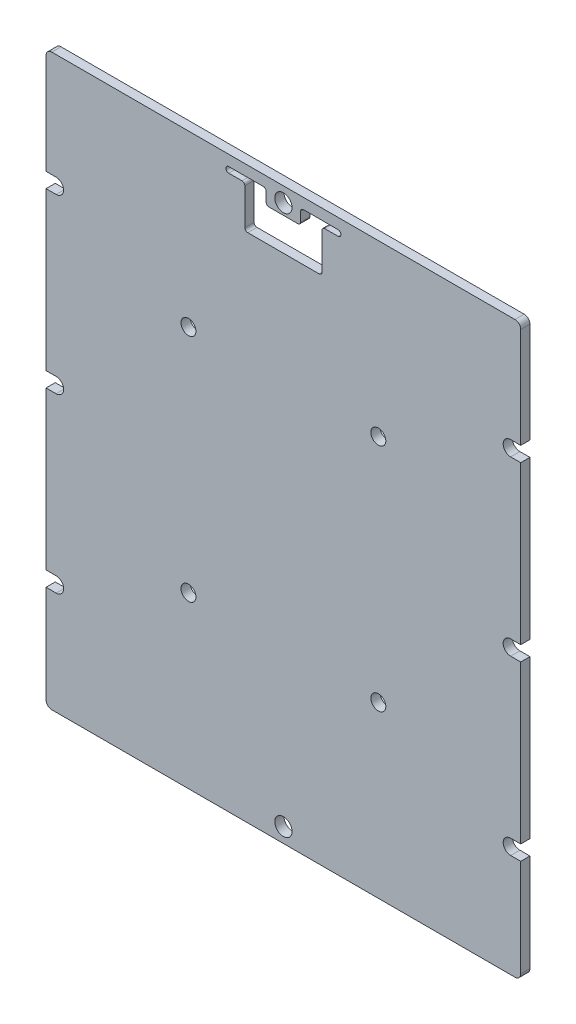
SolidWorks part; units mm, degrees
material "FR4_stuffedProtoboard"
ref_plane "Front Plane" through (0, 0, 0) normal (0, 0, 1) x (1, 0, 0)
ref_plane "Top Plane" through (0, 0, 0) normal (0, 1, 0) x (1, 0, 0)
ref_plane "Right Plane" through (0, 0, 0) normal (1, 0, 0) x (0, 0, -1)
sketch "Sketch2" plane through (0, 0, 0) normal (0, 0, 1) x (1, 0, 0)
  line L0 (39, 49.75) -> (-39, 49.75) construction
  line L1 (-41.5, 49.75) -> (41.5, 49.75) construction
  line L2 (-41.5, 49.75) -> (-41.5, -49.75) construction
  line L3 (-41.5, -49.75) -> (41.5, -49.75) construction
  line L4 (41.5, 49.75) -> (41.5, -49.75) construction
  line L5 (-41.5, 49.75) -> (41.5, -49.75) construction
  line L6 (-41.5, -49.75) -> (41.5, 49.75) construction
  line L7 (41.5, 52.25) -> (41.5, 40.15) construction
  line L8 (-41.5, 49.75) -> (41.5, 49.75) construction
  line L9 (41.5, 49.75) -> (41.5, -49.75) construction
  line L10 (-41.5, -49.75) -> (41.5, -49.75) construction
  line L11 (-41.5, 49.75) -> (-41.5, -49.75) construction
  line L12 (-37, -31.85) -> (37, -31.85) construction
  line L13 (-37, -30.25) -> (37, -30.25) construction
  line L14 (-37, -21.85) -> (37, -21.85) construction
  line L15 (-37, -20.25) -> (37, -20.25) construction
  line L16 (-37, -11.85) -> (37, -11.85) construction
  line L17 (-37, -10.25) -> (37, -10.25) construction
  line L18 (-37, -1.85) -> (37, -1.85) construction
  line L19 (-37, -0.25) -> (37, -0.25) construction
  line L20 (-37, 8.15) -> (37, 8.15) construction
  line L21 (-37, 9.75) -> (37, 9.75) construction
  line L22 (-37, 18.15) -> (37, 18.15) construction
  line L23 (-37, 19.75) -> (37, 19.75) construction
  line L24 (-37, 28.15) -> (37, 28.15) construction
  line L25 (-37, 29.75) -> (37, 29.75) construction
  line L26 (-37, 38.15) -> (37, 38.15) construction
  line L27 (-37, 39.75) -> (37, 39.75) construction
  line L28 (-37, -31.85) -> (37, -31.85) construction
  line L29 (-37, -30.25) -> (37, -30.25) construction
  line L30 (-37, -21.85) -> (37, -21.85) construction
  line L31 (-37, -20.25) -> (37, -20.25) construction
  line L32 (-37, -11.85) -> (37, -11.85) construction
  line L33 (-37, -10.25) -> (37, -10.25) construction
  line L34 (-37, -1.85) -> (37, -1.85) construction
  line L35 (-37, -0.25) -> (37, -0.25) construction
  line L36 (-37, 8.15) -> (37, 8.15) construction
  line L37 (-37, 9.75) -> (37, 9.75) construction
  line L38 (-37, 18.15) -> (37, 18.15) construction
  line L39 (-37, 19.75) -> (37, 19.75) construction
  line L40 (-37, 28.15) -> (37, 28.15) construction
  line L41 (-37, 29.75) -> (37, 29.75) construction
  line L42 (-37, 38.15) -> (37, 38.15) construction
  line L43 (-37, 39.75) -> (37, 39.75) construction
  line L44 (-37, -40.25) -> (37, -40.25) construction
  line L45 (-37, -41.85) -> (37, -41.85) construction
  line L46 (-41.5, 52.25) -> (-41.5, 40.15) construction
  line L47 (39, -49.75) -> (-39, -49.75) construction
  line L48 (41.5, -31.7) -> (41.5, -52.25) construction
  line L49 (-41.25, 49.5) -> (41.25, 49.5)
  line L50 (41.25, 49.5) -> (41.25, -49.5)
  line L51 (-41.25, -49.5) -> (41.25, -49.5)
  line L52 (-41.25, 49.5) -> (-41.25, -49.5)
  circle A0 centre (0, 46.95) radius 1.5 construction
  circle A1 centre (0, 46.95) radius 0.8 construction
  circle A2 centre (0, 46.95) radius 1.5 construction
  circle A3 centre (0, 46.95) radius 0.8
  circle A4 centre (-39.5, -30.25) radius 0.8 construction
  circle A5 centre (-39.5, -0.25) radius 0.8 construction
  circle A6 centre (-39.5, 29.75) radius 0.8 construction
  circle A7 centre (-39.5, -30.25) radius 0.8
  circle A8 centre (-39.5, -0.25) radius 0.8
  circle A9 centre (-39.5, 29.75) radius 0.8
  circle A10 centre (39.5, -30.25) radius 0.8 construction
  circle A11 centre (39.5, -0.25) radius 0.8 construction
  circle A12 centre (39.5, 29.75) radius 0.8 construction
  circle A13 centre (39.5, -30.25) radius 0.8
  circle A14 centre (39.5, -0.25) radius 0.8
  circle A15 centre (39.5, 29.75) radius 0.8
  circle A16 centre (0, -46.95) radius 0.8 construction
  circle A17 centre (0, -46.95) radius 0.8
  circle A18 centre (0, -46.95) radius 1.5 construction
  circle A19 centre (0, -46.95) radius 1.5
  circle A20 centre (-16.5, 20) radius 1.75 construction
  circle A21 centre (-16.5, 20) radius 0.8 construction
  circle A22 centre (-16.5, 20) radius 1.75 construction
  circle A23 centre (-16.5, 20) radius 0.8
  circle A24 centre (16.5, 20) radius 1.75 construction
  circle A25 centre (16.5, 20) radius 0.8 construction
  circle A26 centre (16.5, 20) radius 1.75 construction
  circle A27 centre (16.5, 20) radius 0.8
  circle A28 centre (16.5, -20) radius 1.75 construction
  circle A29 centre (-16.5, -20) radius 1.75 construction
  circle A30 centre (16.5, -20) radius 1.75 construction
  circle A31 centre (-16.5, -20) radius 1.75 construction
  circle A32 centre (-16.5, -20) radius 0.8 construction
  circle A33 centre (-16.5, -20) radius 0.8
  circle A34 centre (16.5, -20) radius 0.8 construction
  circle A35 centre (16.5, -20) radius 0.8
  point P0 (0, 0)
  point P74 (0, -40.25)
  point P75 (0, -31.85)
  point P76 (0, -41.85)
  dimension "D2" = 10
  dimension "D3" = 1.6
  dimension "D1" = 0.25
extrude "pcb extrude" add sketch "Sketch2" along normal mid plane 1.6 contours L4 L1 L2 L3 A2 | A2 A3 | L2 L1 L4 L3 region at (0, 0.0296, 0)
sketch "connector locations" plane through (0, 0, 0.8) normal (0, 0, 1) x (1, 0, 0)
  line L0 (34.5, 45.75) -> (4.5, 45.75) construction
  line L1 (-2.5, 44.75) -> (2.5, 44.75) construction
  line L2 (-4.5, 45.75) -> (-34.5, 45.75) construction
  line L3 (34.5, 45.75) -> (4.5, 45.75)
  line L4 (-2.5, 44.75) -> (2.5, 44.75)
  line L5 (-4.5, 45.75) -> (-34.5, 45.75)
  line L6 (-37, 43.25) -> (-37, -43.25) construction
  line L7 (-37, 43.25) -> (-37, -43.25)
  line L8 (37, -43.25) -> (37, 43.25) construction
  line L9 (37, -43.25) -> (37, 43.25)
  line L10 (4.5, -45.75) -> (34.5, -45.75) construction
  line L11 (4.5, -45.75) -> (34.5, -45.75)
  line L12 (-34.5, -45.75) -> (-4.5, -45.75) construction
  line L13 (-2.5, -44.75) -> (2.5, -44.75) construction
  line L14 (-34.5, -45.75) -> (-4.5, -45.75)
  line L15 (-2.5, -44.75) -> (2.5, -44.75)
  line L16 (-37, 39.75) -> (37, 39.75) construction
  line L17 (-33.9182, 41.909) -> (-9.2802, 41.909)
  line L18 (-33.9182, 41.909) -> (-33.9182, 43.306)
  line L19 (-33.9182, 43.306) -> (-9.2802, 43.306)
  line L20 (-9.2802, 41.909) -> (-9.2802, 43.306)
  line L21 (-33.9182, 41.909) -> (-9.2802, 43.306) construction
  line L22 (-33.9182, 43.306) -> (-9.2802, 41.909) construction
  line L23 (-33.9182, 33.306) -> (-22.0818, 33.306)
  line L24 (-33.9182, 33.306) -> (-33.9182, 31.909)
  line L25 (-33.9182, 31.909) -> (-22.0818, 31.909)
  line L26 (-22.0818, 33.306) -> (-22.0818, 31.909)
  line L27 (-33.9182, 33.306) -> (-22.0818, 31.909) construction
  line L28 (-33.9182, 31.909) -> (-22.0818, 33.306) construction
  line L29 (-12.319, 33.306) -> (12.319, 33.306)
  line L30 (-12.319, 33.306) -> (-12.319, 31.909)
  line L31 (-12.319, 31.909) -> (12.319, 31.909)
  line L32 (12.319, 33.306) -> (12.319, 31.909)
  line L33 (-12.319, 33.306) -> (12.319, 31.909) construction
  line L34 (-12.319, 31.909) -> (12.319, 33.306) construction
  line L35 (-33.9182, 23.306) -> (-22.0818, 23.306)
  line L36 (-33.9182, 23.306) -> (-33.9182, 21.909)
  line L37 (-33.9182, 21.909) -> (-22.0818, 21.909)
  line L38 (-33.9182, 23.306) -> (-22.0818, 21.909) construction
  line L39 (-33.9182, 21.909) -> (-22.0818, 23.306) construction
  line L40 (-22.0818, 23.306) -> (-22.0818, 21.909)
  line L41 (-12.319, 23.306) -> (-12.319, 21.909)
  line L42 (-12.319, 23.306) -> (12.319, 23.306)
  line L43 (-12.319, 21.909) -> (12.319, 21.909)
  line L44 (-12.319, 23.306) -> (12.319, 21.909) construction
  line L45 (-12.319, 21.909) -> (12.319, 23.306) construction
  line L46 (12.319, 23.306) -> (12.319, 21.909)
  line L47 (-33.9182, 13.306) -> (-22.0818, 13.306)
  line L48 (-33.9182, 13.306) -> (-33.9182, 11.909)
  line L49 (-33.9182, 11.909) -> (-22.0818, 11.909)
  line L50 (-33.9182, 13.306) -> (-22.0818, 11.909) construction
  line L51 (-33.9182, 11.909) -> (-22.0818, 13.306) construction
  line L52 (-22.0818, 13.306) -> (-22.0818, 11.909)
  line L53 (-12.319, 13.306) -> (-12.319, 11.909)
  line L54 (-12.319, 13.306) -> (12.319, 13.306)
  line L55 (-12.319, 11.909) -> (12.319, 11.909)
  line L56 (-12.319, 13.306) -> (12.319, 11.909) construction
  line L57 (-12.319, 11.909) -> (12.319, 13.306) construction
  line L58 (12.319, 13.306) -> (12.319, 11.909)
  line L59 (-33.9182, 3.306) -> (-22.0818, 3.306)
  line L60 (-33.9182, 3.306) -> (-33.9182, 1.909)
  line L61 (-33.9182, 1.909) -> (-22.0818, 1.909)
  line L62 (-33.9182, 3.306) -> (-22.0818, 1.909) construction
  line L63 (-33.9182, 1.909) -> (-22.0818, 3.306) construction
  line L64 (-22.0818, 3.306) -> (-22.0818, 1.909)
  line L65 (-12.319, 3.306) -> (-12.319, 1.909)
  line L66 (-12.319, 3.306) -> (12.319, 3.306)
  line L67 (-12.319, 1.909) -> (12.319, 1.909)
  line L68 (-12.319, 3.306) -> (12.319, 1.909) construction
  line L69 (-12.319, 1.909) -> (12.319, 3.306) construction
  line L70 (12.319, 3.306) -> (12.319, 1.909)
  line L71 (-33.9182, -6.694) -> (-22.0818, -6.694)
  line L72 (-33.9182, -6.694) -> (-33.9182, -8.091)
  line L73 (-33.9182, -8.091) -> (-22.0818, -8.091)
  line L74 (-33.9182, -6.694) -> (-22.0818, -8.091) construction
  line L75 (-33.9182, -8.091) -> (-22.0818, -6.694) construction
  line L76 (-22.0818, -6.694) -> (-22.0818, -8.091)
  line L77 (-12.319, -6.694) -> (-12.319, -8.091)
  line L78 (-12.319, -6.694) -> (12.319, -6.694)
  line L79 (-12.319, -8.091) -> (12.319, -8.091)
  line L80 (-12.319, -6.694) -> (12.319, -8.091) construction
  line L81 (-12.319, -8.091) -> (12.319, -6.694) construction
  line L82 (12.319, -6.694) -> (12.319, -8.091)
  line L83 (-33.9182, -16.694) -> (-22.0818, -16.694)
  line L84 (-33.9182, -16.694) -> (-33.9182, -18.091)
  line L85 (-33.9182, -18.091) -> (-22.0818, -18.091)
  line L86 (-33.9182, -16.694) -> (-22.0818, -18.091) construction
  line L87 (-33.9182, -18.091) -> (-22.0818, -16.694) construction
  line L88 (-22.0818, -16.694) -> (-22.0818, -18.091)
  line L89 (-12.319, -16.694) -> (-12.319, -18.091)
  line L90 (-12.319, -16.694) -> (12.319, -16.694)
  line L91 (-12.319, -18.091) -> (12.319, -18.091)
  line L92 (-12.319, -16.694) -> (12.319, -18.091) construction
  line L93 (-12.319, -18.091) -> (12.319, -16.694) construction
  line L94 (12.319, -16.694) -> (12.319, -18.091)
  line L95 (-33.9182, -26.694) -> (-22.0818, -26.694)
  line L96 (-33.9182, -26.694) -> (-33.9182, -28.091)
  line L97 (-33.9182, -28.091) -> (-22.0818, -28.091)
  line L98 (-33.9182, -26.694) -> (-22.0818, -28.091) construction
  line L99 (-33.9182, -28.091) -> (-22.0818, -26.694) construction
  line L100 (-22.0818, -26.694) -> (-22.0818, -28.091)
  line L101 (-12.319, -26.694) -> (-12.319, -28.091)
  line L102 (-12.319, -26.694) -> (12.319, -26.694)
  line L103 (-12.319, -28.091) -> (12.319, -28.091)
  line L104 (-12.319, -26.694) -> (12.319, -28.091) construction
  line L105 (-12.319, -28.091) -> (12.319, -26.694) construction
  line L106 (12.319, -26.694) -> (12.319, -28.091)
  line L107 (-33.9182, -36.694) -> (-22.0818, -36.694)
  line L108 (-33.9182, -36.694) -> (-33.9182, -38.091)
  line L109 (-33.9182, -38.091) -> (-22.0818, -38.091)
  line L110 (-33.9182, -36.694) -> (-22.0818, -38.091) construction
  line L111 (-33.9182, -38.091) -> (-22.0818, -36.694) construction
  line L112 (-22.0818, -36.694) -> (-22.0818, -38.091)
  line L113 (-12.319, -36.694) -> (-12.319, -38.091)
  line L114 (-12.319, -36.694) -> (12.319, -36.694)
  line L115 (-12.319, -38.091) -> (12.319, -38.091)
  line L116 (-12.319, -36.694) -> (12.319, -38.091) construction
  line L117 (-12.319, -38.091) -> (12.319, -36.694) construction
  line L118 (12.319, -36.694) -> (12.319, -38.091)
  line L119 (0, 32.6075) -> (0, 22.6075) construction
  line L120 (-37, 29.75) -> (37, 29.75) construction
  line L121 (32.92, 41.02) -> (35.08, 38.84) construction
  line L122 (32.92, 38.84) -> (35.08, 41.02) construction
  line L123 (26.92, 38.84) -> (29.08, 41.02) construction
  line L124 (26.92, 41.02) -> (29.08, 38.84) construction
  line L125 (20.92, 38.84) -> (23.08, 41.02) construction
  line L126 (20.92, 41.02) -> (23.08, 38.84) construction
  line L127 (26.92, 28.84) -> (29.08, 31.02) construction
  line L128 (26.92, 31.02) -> (29.08, 28.84) construction
  line L129 (20.92, 28.84) -> (23.08, 31.02) construction
  line L130 (20.92, 31.02) -> (23.08, 28.84) construction
  line L131 (26.92, 18.84) -> (29.08, 21.02) construction
  line L132 (26.92, 21.02) -> (29.08, 18.84) construction
  line L133 (20.92, 18.84) -> (23.08, 21.02) construction
  line L134 (20.92, 21.02) -> (23.08, 18.84) construction
  line L135 (26.92, 8.84) -> (29.08, 11.02) construction
  line L136 (26.92, 11.02) -> (29.08, 8.84) construction
  line L137 (20.92, 8.84) -> (23.08, 11.02) construction
  line L138 (20.92, 11.02) -> (23.08, 8.84) construction
  line L139 (26.92, -1.16) -> (29.08, 1.02) construction
  line L140 (26.92, 1.02) -> (29.08, -1.16) construction
  line L141 (20.92, -1.16) -> (23.08, 1.02) construction
  line L142 (20.92, 1.02) -> (23.08, -1.16) construction
  line L143 (26.92, -11.16) -> (29.08, -8.98) construction
  line L144 (26.92, -8.98) -> (29.08, -11.16) construction
  line L145 (20.92, -11.16) -> (23.08, -8.98) construction
  line L146 (20.92, -8.98) -> (23.08, -11.16) construction
  line L147 (26.92, -21.16) -> (29.08, -18.98) construction
  line L148 (26.92, -18.98) -> (29.08, -21.16) construction
  line L149 (20.92, -21.16) -> (23.08, -18.98) construction
  line L150 (20.92, -18.98) -> (23.08, -21.16) construction
  line L151 (26.92, -31.16) -> (29.08, -28.98) construction
  line L152 (26.92, -28.98) -> (29.08, -31.16) construction
  line L153 (20.92, -31.16) -> (23.08, -28.98) construction
  line L154 (20.92, -28.98) -> (23.08, -31.16) construction
  line L155 (26.92, -41.16) -> (29.08, -38.98) construction
  line L156 (26.92, -38.98) -> (29.08, -41.16) construction
  line L157 (20.92, -41.16) -> (23.08, -38.98) construction
  line L158 (20.92, -38.98) -> (23.08, -41.16) construction
  line L159 (32.92, 28.84) -> (35.08, 31.02) construction
  line L160 (32.92, 31.02) -> (35.08, 28.84) construction
  line L161 (32.92, 18.84) -> (35.08, 21.02) construction
  line L162 (32.92, 21.02) -> (35.08, 18.84) construction
  line L163 (32.92, 8.84) -> (35.08, 11.02) construction
  line L164 (32.92, 11.02) -> (35.08, 8.84) construction
  line L165 (32.92, -1.16) -> (35.08, 1.02) construction
  line L166 (32.92, 1.02) -> (35.08, -1.16) construction
  line L167 (32.92, -11.16) -> (35.08, -8.98) construction
  line L168 (32.92, -8.98) -> (35.08, -11.16) construction
  line L169 (32.92, -21.16) -> (35.08, -18.98) construction
  line L170 (32.92, -18.98) -> (35.08, -21.16) construction
  line L171 (32.92, -31.16) -> (35.08, -28.98) construction
  line L172 (32.92, -28.98) -> (35.08, -31.16) construction
  line L173 (32.92, -41.16) -> (35.08, -38.98) construction
  line L174 (32.92, -38.98) -> (35.08, -41.16) construction
  line L175 (34, 39.93) -> (28, 39.93) construction
  line L176 (34, 39.93) -> (34, 29.93) construction
  arc A0 (4.5, 45.75) -> (2.5, 44.75) centre (4.5, 43.25) ccw construction
  arc A1 (-2.5, 44.75) -> (-4.5, 45.75) centre (-4.5, 43.25) ccw construction
  arc A2 (-34.5, 45.75) -> (-37, 43.25) centre (-34.5, 43.25) ccw construction
  arc A3 (4.5, 45.75) -> (2.5, 44.75) centre (4.5, 43.25) ccw
  arc A4 (-2.5, 44.75) -> (-4.5, 45.75) centre (-4.5, 43.25) ccw
  arc A5 (-34.5, 45.75) -> (-37, 43.25) centre (-34.5, 43.25) ccw
  arc A6 (37, 43.25) -> (34.5, 45.75) centre (34.5, 43.25) ccw construction
  arc A7 (37, 43.25) -> (34.5, 45.75) centre (34.5, 43.25) ccw
  arc A8 (34.5, -45.75) -> (37, -43.25) centre (34.5, -43.25) ccw construction
  arc A9 (34.5, -45.75) -> (37, -43.25) centre (34.5, -43.25) ccw
  arc A10 (-37, -43.25) -> (-34.5, -45.75) centre (-34.5, -43.25) ccw construction
  arc A11 (-4.5, -45.75) -> (-2.5, -44.75) centre (-4.5, -43.25) ccw construction
  arc A12 (2.5, -44.75) -> (4.5, -45.75) centre (4.5, -43.25) ccw construction
  arc A13 (-37, -43.25) -> (-34.5, -45.75) centre (-34.5, -43.25) ccw
  arc A14 (-4.5, -45.75) -> (-2.5, -44.75) centre (-4.5, -43.25) ccw
  arc A15 (2.5, -44.75) -> (4.5, -45.75) centre (4.5, -43.25) ccw
  circle A16 centre (-21.5992, 42.6075) radius 0.5
  circle A17 centre (0, 32.6075) radius 0.5
  circle A18 centre (-28, 32.6075) radius 0.5
  circle A19 centre (-28, 22.6075) radius 0.5
  circle A20 centre (0, 22.6075) radius 0.5
  circle A21 centre (-28, 12.6075) radius 0.5
  circle A22 centre (0, 12.6075) radius 0.5
  circle A23 centre (-28, 2.6075) radius 0.5
  circle A24 centre (0, 2.6075) radius 0.5
  circle A25 centre (-28, -7.3925) radius 0.5
  circle A26 centre (0, -7.3925) radius 0.5
  circle A27 centre (-28, -17.3925) radius 0.5
  circle A28 centre (0, -17.3925) radius 0.5
  circle A29 centre (-28, -27.3925) radius 0.5
  circle A30 centre (0, -27.3925) radius 0.5
  circle A31 centre (-28, -37.3925) radius 0.5
  circle A32 centre (0, -37.3925) radius 0.5
  circle A33 centre (35.08, 41.02) radius 0.32
  circle A34 centre (32.92, 38.84) radius 0.32
  circle A35 centre (35.08, 38.84) radius 0.32
  circle A36 centre (32.92, 41.02) radius 0.32
  circle A37 centre (26.92, 41.02) radius 0.32
  circle A38 centre (29.08, 41.02) radius 0.32
  circle A39 centre (26.92, 38.84) radius 0.32
  circle A40 centre (29.08, 38.84) radius 0.32
  circle A41 centre (20.92, 41.02) radius 0.32
  circle A42 centre (23.08, 41.02) radius 0.32
  circle A43 centre (20.92, 38.84) radius 0.32
  circle A44 centre (23.08, 38.84) radius 0.32
  circle A45 centre (26.92, 31.02) radius 0.32
  circle A46 centre (29.08, 31.02) radius 0.32
  circle A47 centre (26.92, 28.84) radius 0.32
  circle A48 centre (29.08, 28.84) radius 0.32
  circle A49 centre (20.92, 31.02) radius 0.32
  circle A50 centre (23.08, 31.02) radius 0.32
  circle A51 centre (20.92, 28.84) radius 0.32
  circle A52 centre (23.08, 28.84) radius 0.32
  circle A53 centre (26.92, 21.02) radius 0.32
  circle A54 centre (29.08, 21.02) radius 0.32
  circle A55 centre (26.92, 18.84) radius 0.32
  circle A56 centre (29.08, 18.84) radius 0.32
  circle A57 centre (20.92, 21.02) radius 0.32
  circle A58 centre (23.08, 21.02) radius 0.32
  circle A59 centre (20.92, 18.84) radius 0.32
  circle A60 centre (23.08, 18.84) radius 0.32
  circle A61 centre (26.92, 11.02) radius 0.32
  circle A62 centre (29.08, 11.02) radius 0.32
  circle A63 centre (26.92, 8.84) radius 0.32
  circle A64 centre (29.08, 8.84) radius 0.32
  circle A65 centre (20.92, 11.02) radius 0.32
  circle A66 centre (23.08, 11.02) radius 0.32
  circle A67 centre (20.92, 8.84) radius 0.32
  circle A68 centre (23.08, 8.84) radius 0.32
  circle A69 centre (26.92, 1.02) radius 0.32
  circle A70 centre (29.08, 1.02) radius 0.32
  circle A71 centre (26.92, -1.16) radius 0.32
  circle A72 centre (29.08, -1.16) radius 0.32
  circle A73 centre (20.92, 1.02) radius 0.32
  circle A74 centre (23.08, 1.02) radius 0.32
  circle A75 centre (20.92, -1.16) radius 0.32
  circle A76 centre (23.08, -1.16) radius 0.32
  circle A77 centre (26.92, -8.98) radius 0.32
  circle A78 centre (29.08, -8.98) radius 0.32
  circle A79 centre (26.92, -11.16) radius 0.32
  circle A80 centre (29.08, -11.16) radius 0.32
  circle A81 centre (20.92, -8.98) radius 0.32
  circle A82 centre (23.08, -8.98) radius 0.32
  circle A83 centre (20.92, -11.16) radius 0.32
  circle A84 centre (23.08, -11.16) radius 0.32
  circle A85 centre (26.92, -18.98) radius 0.32
  circle A86 centre (29.08, -18.98) radius 0.32
  circle A87 centre (26.92, -21.16) radius 0.32
  circle A88 centre (29.08, -21.16) radius 0.32
  circle A89 centre (20.92, -18.98) radius 0.32
  circle A90 centre (23.08, -18.98) radius 0.32
  circle A91 centre (20.92, -21.16) radius 0.32
  circle A92 centre (23.08, -21.16) radius 0.32
  circle A93 centre (26.92, -28.98) radius 0.32
  circle A94 centre (29.08, -28.98) radius 0.32
  circle A95 centre (26.92, -31.16) radius 0.32
  circle A96 centre (29.08, -31.16) radius 0.32
  circle A97 centre (20.92, -28.98) radius 0.32
  circle A98 centre (23.08, -28.98) radius 0.32
  circle A99 centre (20.92, -31.16) radius 0.32
  circle A100 centre (23.08, -31.16) radius 0.32
  circle A101 centre (26.92, -38.98) radius 0.32
  circle A102 centre (29.08, -38.98) radius 0.32
  circle A103 centre (26.92, -41.16) radius 0.32
  circle A104 centre (29.08, -41.16) radius 0.32
  circle A105 centre (20.92, -38.98) radius 0.32
  circle A106 centre (23.08, -38.98) radius 0.32
  circle A107 centre (20.92, -41.16) radius 0.32
  circle A108 centre (23.08, -41.16) radius 0.32
  circle A109 centre (32.92, 31.02) radius 0.32
  circle A110 centre (35.08, 31.02) radius 0.32
  circle A111 centre (32.92, 28.84) radius 0.32
  circle A112 centre (35.08, 28.84) radius 0.32
  circle A113 centre (32.92, 21.02) radius 0.32
  circle A114 centre (35.08, 21.02) radius 0.32
  circle A115 centre (32.92, 18.84) radius 0.32
  circle A116 centre (35.08, 18.84) radius 0.32
  circle A117 centre (32.92, 11.02) radius 0.32
  circle A118 centre (35.08, 11.02) radius 0.32
  circle A119 centre (32.92, 8.84) radius 0.32
  circle A120 centre (35.08, 8.84) radius 0.32
  circle A121 centre (32.92, 1.02) radius 0.32
  circle A122 centre (35.08, 1.02) radius 0.32
  circle A123 centre (32.92, -1.16) radius 0.32
  circle A124 centre (35.08, -1.16) radius 0.32
  circle A125 centre (32.92, -8.98) radius 0.32
  circle A126 centre (35.08, -8.98) radius 0.32
  circle A127 centre (32.92, -11.16) radius 0.32
  circle A128 centre (35.08, -11.16) radius 0.32
  circle A129 centre (32.92, -18.98) radius 0.32
  circle A130 centre (35.08, -18.98) radius 0.32
  circle A131 centre (32.92, -21.16) radius 0.32
  circle A132 centre (35.08, -21.16) radius 0.32
  circle A133 centre (32.92, -28.98) radius 0.32
  circle A134 centre (35.08, -28.98) radius 0.32
  circle A135 centre (32.92, -31.16) radius 0.32
  circle A136 centre (35.08, -31.16) radius 0.32
  circle A137 centre (32.92, -38.98) radius 0.32
  circle A138 centre (35.08, -38.98) radius 0.32
  circle A139 centre (32.92, -41.16) radius 0.32
  circle A140 centre (35.08, -41.16) radius 0.32
  point P18 (-21.5992, 42.6075)
  point P29 (-28, 32.6075)
  point P34 (0, 32.6075)
  point P50 (-28, 22.6075)
  point P55 (0, 22.6075)
  point P64 (-28, 12.6075)
  point P69 (0, 12.6075)
  point P78 (-28, 2.6075)
  point P83 (0, 2.6075)
  point P92 (-28, -7.3925)
  point P97 (0, -7.3925)
  point P106 (-28, -17.3925)
  point P111 (0, -17.3925)
  point P120 (-28, -27.3925)
  point P125 (0, -27.3925)
  point P134 (-28, -37.3925)
  point P139 (0, -37.3925)
  point P165 (34, 39.93)
  point P170 (28, 39.93)
  point P179 (22, 39.93)
  point P188 (28, 29.93)
  point P197 (22, 29.93)
  point P206 (28, 19.93)
  point P215 (22, 19.93)
  point P224 (28, 9.93)
  point P233 (22, 9.93)
  point P242 (28, -0.07)
  point P251 (22, -0.07)
  point P260 (28, -10.07)
  point P269 (22, -10.07)
  point P278 (28, -20.07)
  point P287 (22, -20.07)
  point P296 (28, -30.07)
  point P305 (22, -30.07)
  point P314 (28, -40.07)
  point P323 (22, -40.07)
  point P332 (34, 29.93)
  point P341 (34, 19.93)
  point P350 (34, 9.93)
  point P359 (34, -0.07)
  point P368 (34, -10.07)
  point P377 (34, -20.07)
  point P386 (34, -30.07)
  point P395 (34, -40.07)
  dimension "D4" = 1
  dimension "D5" = 11.8364
  dimension "D10" = 0.64
  dimension "D1" = 24.638
  dimension "D2" = 1.397
  dimension "D3" = 2.159
  dimension "D6" = 28
  dimension "D8" = 10
  dimension "D9" = 2.159
  dimension "D11" = 2.18
  dimension "D12" = 2.16
  dimension "D13" = 0.18
  dimension "D14" = 34
  dimension "D17" = 6
  dimension "D18" = 10
  dimension "D7" = 8
  dimension "D15" = 3
  dimension "D16" = 9
fillet "corner fillets" radius 1 4 edges at (41.25, -49.5, 0) (-41.25, -49.5, 0) (41.25, 49.5, 0) (-41.25, 49.5, 0)
sketch "Sketch4" plane through (0, 0, 0.8) normal (0, 0, 1) x (1, 0, 0)
  line L0 (0, 46.95) -> (0, 39.35) construction
  line L1 (6.7, 39.35) -> (-6.7, 39.35)
  line L2 (-6.7, 39.35) -> (-6.7, 46.65)
  line L3 (-6.7, 46.65) -> (-9.5, 46.65)
  line L4 (-4.5, 45.75) -> (-34.5, 45.75) construction
  line L5 (-9.5, 47.65) -> (-3, 47.65)
  line L6 (-3, 47.65) -> (-3, 45.05)
  line L7 (-3, 45.05) -> (3, 45.05)
  line L8 (3, 47.65) -> (3, 45.05)
  line L9 (6.7, 39.35) -> (6.7, 46.65)
  line L10 (6.7, 46.65) -> (9.5, 46.65)
  line L11 (9.5, 47.65) -> (3, 47.65)
  arc A0 (-9.5, 47.65) -> (-9.5, 46.65) centre (-9.5, 47.15) ccw
  arc A1 (9.5, 47.65) -> (9.5, 46.65) centre (9.5, 47.15) cw
  circle A2 centre (0, 46.95) radius 1.5
  point P17 (0, 45.05)
  dimension "D3" = 1
  dimension "D8" = 3
  dimension "D1" = 3
  dimension "D2" = 9.5
  dimension "D4" = 0.9
  dimension "D5" = 7.3
  dimension "D6" = 2.6
  dimension "D7" = 3.7
extrude "solar holes" cut sketch "Sketch4" against normal through all
fillet "solar hole fillets" radius 0.5 8 edges at (6.7, 46.65, 0) (3, 47.65, 0) (3, 45.05, 0) (6.7, 39.35, 0) (-6.7, 39.35, 0) (-6.7, 46.65, 0) (-3, 45.05, 0) (-3, 47.65, 0)
sketch "m2 locations" plane through (0, 0, 0.8) normal (0, 0, 1) x (1, 0, 0)
  point P0 (-39.5, 29.75)
  point P1 (-39.5, -0.25)
  point P3 (-39.5, -30.25)
  point P5 (-16.5, -20)
  point P7 (-16.5, 20)
  point P9 (16.5, 20)
  point P11 (16.5, -20)
  point P13 (39.5, -30.25)
  point P15 (39.5, -0.25)
  point P17 (39.5, 29.75)
hole_wizard "M2 Clearance Holes" positions "Sketch8" profile "Sketch9" hole size "M2" standard "ANSI Metric" end condition through all
sketch "Sketch8" plane through (0, 0, 0.8) normal (0, 0, 1) x (1, 0, 0)
  point P0 (-39.5, 29.75)
  point P3 (-39.5, -0.25)
  point P6 (-16.5, 20)
  point P9 (16.5, 20)
  point P12 (16.5, -20)
  point P15 (-16.5, -20)
  point P18 (39.5, 29.75)
  point P21 (39.5, -0.25)
  point P24 (39.5, -30.25)
  point P27 (-39.5, -30.25)
sketch "Sketch9" plane through (-39.5, 29.75, 0.8) normal (1, 0, 0) x (0, -1, 0)
  line L0 (0, 0) -> (0, 1.6)
  line L1 (0, 1.6) -> (1.3, 1.6)
  line L2 (1.3, 1.6) -> (1.3, 0)
  line L5 (1.3, 0) -> (0, 0)
  line L11 (0, -6.35) -> (0, 107.95) construction
  dimension "Thru Hole Dia." = 2.6
  dimension "Thru Hole Depth" = 1.6
sketch "Sketch10" plane through (0, 0, 0.8) normal (0, 0, 1) x (1, 0, 0)
  line L0 (-41.25, 48.5) -> (-41.25, -48.5) construction
  line L1 (-39.5, 31.05) -> (-41.25, 31.05)
  line L2 (-39.5, 31.05) -> (-39.5, 28.45)
  line L3 (-39.5, 28.45) -> (-41.25, 28.45)
  line L4 (-41.25, 31.05) -> (-41.25, 28.45)
  line L5 (41.25, 48.5) -> (41.25, -48.5) construction
  line L6 (-39.5, 1.05) -> (-41.25, 1.05)
  line L7 (-39.5, 1.05) -> (-39.5, -1.55)
  line L8 (-39.5, -1.55) -> (-41.25, -1.55)
  line L9 (-41.25, 1.05) -> (-41.25, -1.55)
  line L10 (-39.5, -28.95) -> (-41.25, -28.95)
  line L11 (-39.5, -28.95) -> (-39.5, -31.55)
  line L12 (-39.5, -31.55) -> (-41.25, -31.55)
  line L13 (-41.25, -28.95) -> (-41.25, -31.55)
  line L14 (39.5, -28.95) -> (41.25, -28.95)
  line L15 (39.5, -28.95) -> (39.5, -31.55)
  line L16 (39.5, -31.55) -> (41.25, -31.55)
  line L17 (41.25, -28.95) -> (41.25, -31.55)
  line L19 (39.5, 1.05) -> (41.25, 1.05)
  line L20 (39.5, 1.05) -> (39.5, -1.55)
  line L21 (39.5, -1.55) -> (41.25, -1.55)
  line L22 (41.25, 1.05) -> (41.25, -1.55)
  line L23 (39.5, 31.05) -> (41.25, 31.05)
  line L24 (39.5, 31.05) -> (39.5, 28.45)
  line L25 (39.5, 28.45) -> (41.25, 28.45)
  line L26 (41.25, 31.05) -> (41.25, 28.45)
  circle A0 centre (-39.5, 29.75) radius 1.3 construction
  circle A1 centre (-39.5, -0.25) radius 1.3 construction
  circle A2 centre (-39.5, -30.25) radius 1.3 construction
  circle A3 centre (39.5, -30.25) radius 1.3 construction
  circle A4 centre (39.5, -0.25) radius 1.3 construction
  circle A5 centre (39.5, 29.75) radius 1.3 construction
  point P43 (-39.5, 29.75)
extrude "Cut-Extrude2" cut sketch "Sketch10" against normal through all
